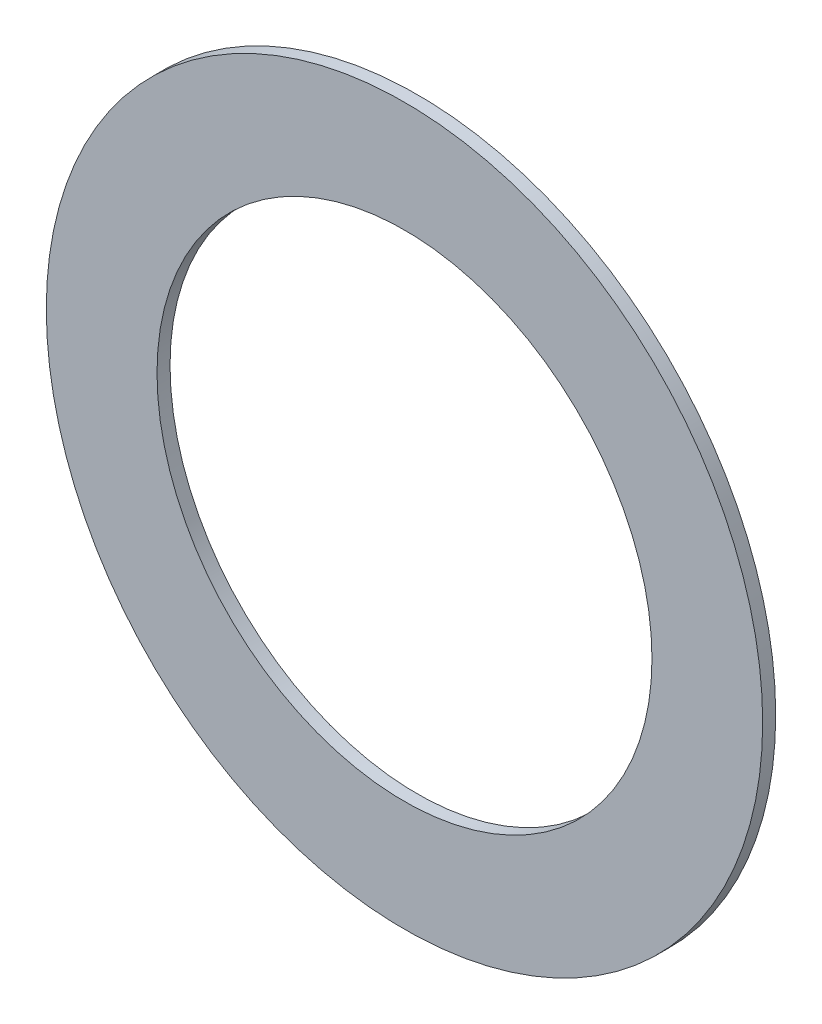
SolidWorks part; units mm, degrees
material "1.4301 (X5CrNi18-10)"
ref_plane "E_Rechts" through (0, 0, 0) normal (0, 0, 1) x (1, 0, 0)
ref_plane "E_Oben" through (0, 0, 0) normal (0, 1, 0) x (1, 0, 0)
ref_plane "E_Vorne" through (0, 0, 0) normal (1, 0, 0) x (0, 0, -1)
ref_axis "A_Drehachse" through (0, 0, -88.99) along (0, 0, 1)
sketch "Skizze1" plane through (0, 0, 0) normal (0, 0, 1) x (1, 0, 0)
  circle A0 centre (0, 0) radius 19
  circle A1 centre (0, 0) radius 27.5
extrude "Aufsatz-Linear austragen1" add sketch "Skizze1" along normal mid plane 1
